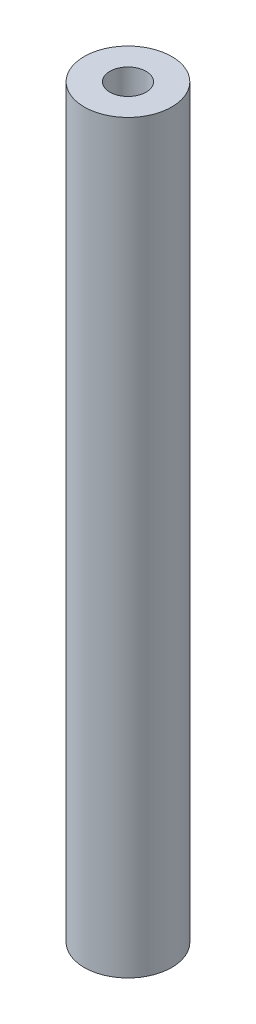
SolidWorks part; units mm, degrees
ref_plane "Front Plane" through (0, 0, 0) normal (0, 0, 1) x (1, 0, 0)
ref_plane "Top Plane" through (0, 0, 0) normal (0, 1, 0) x (1, 0, 0)
ref_plane "Right Plane" through (0, 0, 0) normal (1, 0, 0) x (0, 0, -1)
sketch "Sketch1" plane through (0, 0, 0) normal (0, 1, 0) x (1, 0, 0)
  circle A0 centre (0, 0) radius 2.055
  circle A1 centre (0, 0) radius 0.85
  dimension "D1" = 4.11
  dimension "D2" = 1.7
extrude "Boss-Extrude1" add sketch "Sketch1" along normal mid plane 35
